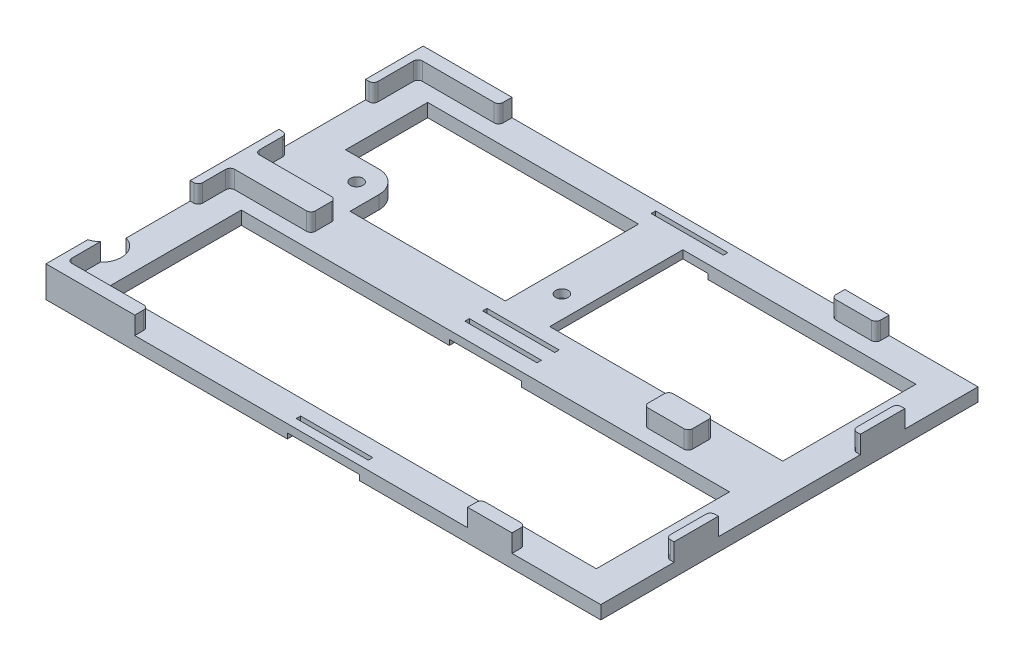
SolidWorks part; units mm, degrees
ref_plane "Front Plane" through (0, 0, 0) normal (0, 0, 1) x (1, 0, 0)
ref_plane "Top Plane" through (0, 0, 0) normal (0, 1, 0) x (1, 0, 0)
ref_plane "Right Plane" through (0, 0, 0) normal (1, 0, 0) x (0, 0, -1)
sketch "Sketch3" plane through (0, 0, 0) normal (0, 1, 0) x (1, 0, 0)
  line L1 (0, 0) -> (158.75, 0)
  line L2 (0, 0) -> (0, 107.95)
  line L3 (0, 107.95) -> (158.75, 107.95)
  line L4 (158.75, 0) -> (158.75, 107.95)
  dimension "D1" = 107.95
  dimension "D2" = 158.75
extrude "Base Extrude" add sketch "Sketch3" along normal blind 3.81
sketch "Sketch4" plane through (0, 3.81, 0) normal (0, 1, 0) x (1, 0, 0)
  line L0 (158.75, 107.95) -> (0, 107.95) construction
  line L1 (69.0562, 105.41) -> (89.6938, 105.41)
  line L2 (69.0562, 105.41) -> (69.0562, 104.14)
  line L3 (69.0562, 104.14) -> (89.6938, 104.14)
  line L4 (89.6938, 105.41) -> (89.6938, 104.14)
  line L5 (69.0562, 57.15) -> (89.6938, 57.15)
  line L6 (69.0562, 57.15) -> (69.0562, 55.88)
  line L7 (69.0562, 55.88) -> (89.6938, 55.88)
  line L8 (89.6938, 57.15) -> (89.6938, 55.88)
  line L9 (69.0563, 52.07) -> (89.6938, 52.07)
  line L10 (69.0563, 52.07) -> (69.0563, 50.8)
  line L11 (69.0563, 50.8) -> (89.6938, 50.8)
  line L12 (89.6938, 52.07) -> (89.6938, 50.8)
  line L13 (69.0563, 3.81) -> (89.6938, 3.81)
  line L14 (69.0563, 3.81) -> (69.0563, 2.54)
  line L15 (69.0563, 2.54) -> (89.6938, 2.54)
  line L16 (89.6938, 3.81) -> (89.6938, 2.54)
  line L17 (0, 0) -> (158.75, 0) construction
  line L18 (9.525, 46.355) -> (149.225, 46.355)
  line L19 (9.525, 99.695) -> (149.225, 99.695)
  line L20 (9.525, 99.695) -> (9.525, 61.595)
  line L21 (9.525, 61.595) -> (149.225, 61.595)
  line L22 (149.225, 99.695) -> (149.225, 61.595)
  line L23 (9.525, 46.355) -> (9.525, 8.255)
  line L24 (9.525, 8.255) -> (149.225, 8.255)
  line L25 (149.225, 46.355) -> (149.225, 8.255)
  line L26 (79.375, 104.14) -> (79.375, 57.15) construction
  line L27 (79.375, 50.8) -> (79.375, 3.81) construction
  point P28 (79.375, 105.41)
  point P29 (79.375, 107.95)
  point P32 (9.525, 80.645)
  point P33 (79.375, 80.645)
  point P34 (9.525, 27.305)
  point P35 (79.375, 99.695)
  point P36 (79.375, 27.305)
  point P40 (79.375, 46.355)
  dimension "D1" = 46.99
  dimension "D2" = 46.99
  dimension "D3" = 1.27
  dimension "D4" = 20.6375
  dimension "D5" = 2.54
  dimension "D6" = 2.54
  dimension "D7" = 38.1
  dimension "D8" = 139.7
extrude "Velcro slits" cut sketch "Sketch4" against normal through all
sketch "Sketch5" plane through (0, 0, 0) normal (0, 0, 1) x (1, 0, 0)
  line L1 (69.0563, 1.524) -> (89.6938, 1.524)
  line L2 (69.0563, 1.524) -> (69.0563, 0)
  line L3 (69.0563, 0) -> (89.6938, 0)
  line L4 (89.6938, 1.524) -> (89.6938, 0)
  line L5 (89.6938, 0) -> (89.6938, 3.81) construction
  line L6 (0, 0) -> (158.75, 0) construction
  line L7 (69.0563, 0) -> (69.0563, 3.81) construction
  dimension "D1" = 1.524
extrude "Passthrough Cut" cut sketch "Sketch5" against normal through all contours L1 L4 L3 L2
sketch "Sketch6" plane through (0, 3.81, 0) normal (0, 1, 0) x (1, 0, 0)
  line L0 (2.286, 16.51) -> (2.286, 3.81)
  line L1 (2.286, 3.81) -> (25.4, 3.81)
  line L2 (25.4, 3.81) -> (25.4, 0)
  line L3 (25.4, 0) -> (0, 0)
  line L4 (0, 0) -> (0, 16.51)
  line L5 (0, 16.51) -> (2.286, 16.51)
  line L6 (2.286, 41.275) -> (2.286, 50.419)
  line L7 (2.286, 50.419) -> (25.4, 50.419)
  line L8 (25.4, 50.419) -> (25.4, 57.531)
  line L9 (25.4, 57.531) -> (2.286, 57.531)
  line L10 (2.286, 57.531) -> (2.286, 66.675)
  line L11 (2.286, 66.675) -> (0, 66.675)
  line L12 (0, 66.675) -> (0, 41.275)
  line L13 (0, 41.275) -> (2.286, 41.275)
  line L14 (0, 91.44) -> (2.286, 91.44)
  line L15 (2.286, 91.44) -> (2.286, 104.14)
  line L19 (0, 107.95) -> (0, 91.44)
  line L20 (79.375, 61.595) -> (79.375, 46.355) construction
  line L21 (9.525, 61.595) -> (149.225, 61.595) construction
  line L22 (149.225, 46.355) -> (9.525, 46.355) construction
  line L23 (79.375, 104.14) -> (79.375, 57.15) construction
  line L28 (69.0562, 104.14) -> (89.6938, 104.14) construction
  line L29 (89.6938, 57.15) -> (69.0562, 57.15) construction
  line L34 (79.375, 50.8) -> (79.375, 3.81) construction
  line L35 (69.0563, 50.8) -> (89.6938, 50.8) construction
  line L36 (89.6938, 3.81) -> (69.0563, 3.81) construction
  line L37 (0, 107.95) -> (0, 0) construction
  line L38 (0, 0) -> (158.75, 0) construction
  line L39 (2.286, 104.14) -> (25.4, 104.14)
  line L40 (25.4, 104.14) -> (25.4, 107.95)
  line L41 (25.4, 107.95) -> (0, 107.95)
  line L42 (158.75, 107.95) -> (0, 107.95) construction
  line L43 (158.75, 0) -> (158.75, 107.95) construction
  line L44 (158.75, 86.995) -> (156.464, 86.995)
  line L45 (158.75, 86.995) -> (158.75, 74.295)
  line L46 (158.75, 74.295) -> (156.464, 74.295)
  line L47 (156.464, 86.995) -> (156.464, 74.295)
  line L49 (158.75, 33.655) -> (156.464, 33.655)
  line L50 (158.75, 33.655) -> (158.75, 20.955)
  line L51 (158.75, 20.955) -> (156.464, 20.955)
  line L52 (156.464, 33.655) -> (156.464, 20.955)
  line L53 (133.35, 107.95) -> (120.65, 107.95)
  line L54 (133.35, 107.95) -> (133.35, 104.14)
  line L55 (133.35, 104.14) -> (120.65, 104.14)
  line L56 (120.65, 107.95) -> (120.65, 104.14)
  line L57 (120.65, 57.531) -> (133.35, 57.531)
  line L58 (120.65, 57.531) -> (120.65, 50.419)
  line L59 (120.65, 50.419) -> (133.35, 50.419)
  line L60 (133.35, 57.531) -> (133.35, 50.419)
  line L61 (133.35, 3.81) -> (120.65, 3.81)
  line L62 (133.35, 3.81) -> (133.35, 0)
  line L63 (133.35, 0) -> (120.65, 0)
  line L64 (120.65, 3.81) -> (120.65, 0)
  point P26 (25.4, 53.975)
  point P27 (79.375, 53.975)
  point P39 (3.175, 80.645)
  point P40 (79.375, 80.645)
  point P41 (79.375, 27.305)
  point P47 (3.175, 27.305)
  point P54 (155.575, 27.305)
  point P71 (156.464, 80.645)
  point P72 (156.464, 27.305)
  point P85 (120.65, 53.975)
  dimension "D1" = 2.286
  dimension "D2" = 12.7
  dimension "D5" = 25.4
  dimension "D6" = 7.112
  dimension "D7" = 3.81
  dimension "D8" = 25.4
  dimension "D9" = 2.286
  dimension "D10" = 12.7
  dimension "D11" = 12.7
  dimension "D12" = 25.4
extrude "Boss-Extrude2" add sketch "Sketch6" along normal blind 5.08
fillet "Fillet1" radius 1.27 24 edges at (156.464, 6.35, -20.955) (156.464, 6.35, -33.655) (156.464, 6.35, -74.295) (156.464, 6.35, -86.995) (120.65, 6.35, -3.81) (133.35, 6.35, -3.81) (133.35, 6.35, -104.14) (120.65, 6.35, -104.14) (120.65, 6.35, -50.419) (120.65, 6.35, -57.531) (133.35, 6.35, -57.531) (133.35, 6.35, -50.419) (2.286, 6.35, -66.675) (2.286, 6.35, -57.531) (25.4, 6.35, -3.81) (2.286, 6.35, -3.81) (2.286, 6.35, -16.51) (25.4, 6.35, -50.419) (25.4, 6.35, -57.531) (2.286, 6.35, -41.275) (2.286, 6.35, -50.419) (25.4, 6.35, -104.14) (2.286, 6.35, -104.14) (2.286, 6.35, -91.44)
sketch "Sketch7" plane through (0, 3.81, 0) normal (0, 1, 0) x (1, 0, 0)
  line L0 (0, 91.44) -> (0, 66.675) construction
  line L1 (120.65, 107.95) -> (25.4, 107.95) construction
  line L2 (19.05, 76.2) -> (9.525, 76.2)
  line L3 (9.525, 99.695) -> (9.525, 61.595) construction
  line L4 (25.4, 69.85) -> (25.4, 61.595)
  line L5 (9.525, 61.595) -> (149.225, 61.595) construction
  line L6 (25.4, 61.595) -> (9.525, 61.595)
  line L7 (9.525, 61.595) -> (9.525, 76.2)
  line L8 (69.85, 99.695) -> (69.85, 61.595)
  line L9 (149.225, 99.695) -> (9.525, 99.695) construction
  line L10 (69.85, 61.595) -> (82.55, 61.595)
  line L11 (82.55, 61.595) -> (82.55, 99.695)
  line L12 (82.55, 99.695) -> (69.85, 99.695)
  circle A0 centre (19.05, 69.85) radius 1.778
  circle A1 centre (76.2, 71.4375) radius 1.778
  arc A2 (25.4, 69.85) -> (19.05, 76.2) centre (19.05, 69.85) ccw
  dimension "D3" = 3.556
  dimension "D6" = 12.7
  dimension "D1" = 57.15
  dimension "D2" = 1.5875
  dimension "D4" = 19.05
  dimension "D5" = 38.1
  dimension "D7" = 12.7
  dimension "D8" = 60.325
extrude "Boss-Extrude3" add sketch "Sketch7" against normal up to surface (3.81 mm away) up to face at (121.0469, 0, -53.975)
sketch "Sketch8" plane through (0, 0, -99.695) normal (0, 0, -1) x (-1, 0, 0)
  line L1 (-82.55, 0) -> (-69.85, 0)
  line L2 (-82.55, 0) -> (-82.55, 1.524)
  line L3 (-82.55, 1.524) -> (-69.85, 1.524)
  line L4 (-69.85, 0) -> (-69.85, 1.524)
extrude "Velcro Slit Through" cut sketch "Sketch8" against normal through all
sketch "Sketch9" plane through (0, 3.81, 0) normal (0, 1, 0) x (1, 0, 0)
  circle A0 centre (-1.5875, 17.4625) radius 5.715
  circle A1 centre (19.05, 69.85) radius 1.778 construction
  dimension "D1" = 52.3875
  dimension "D2" = 20.6375
  dimension "D3" = 11.43
extrude "Cut-Extrude2" cut sketch "Sketch9" against normal through all and the other way through all
